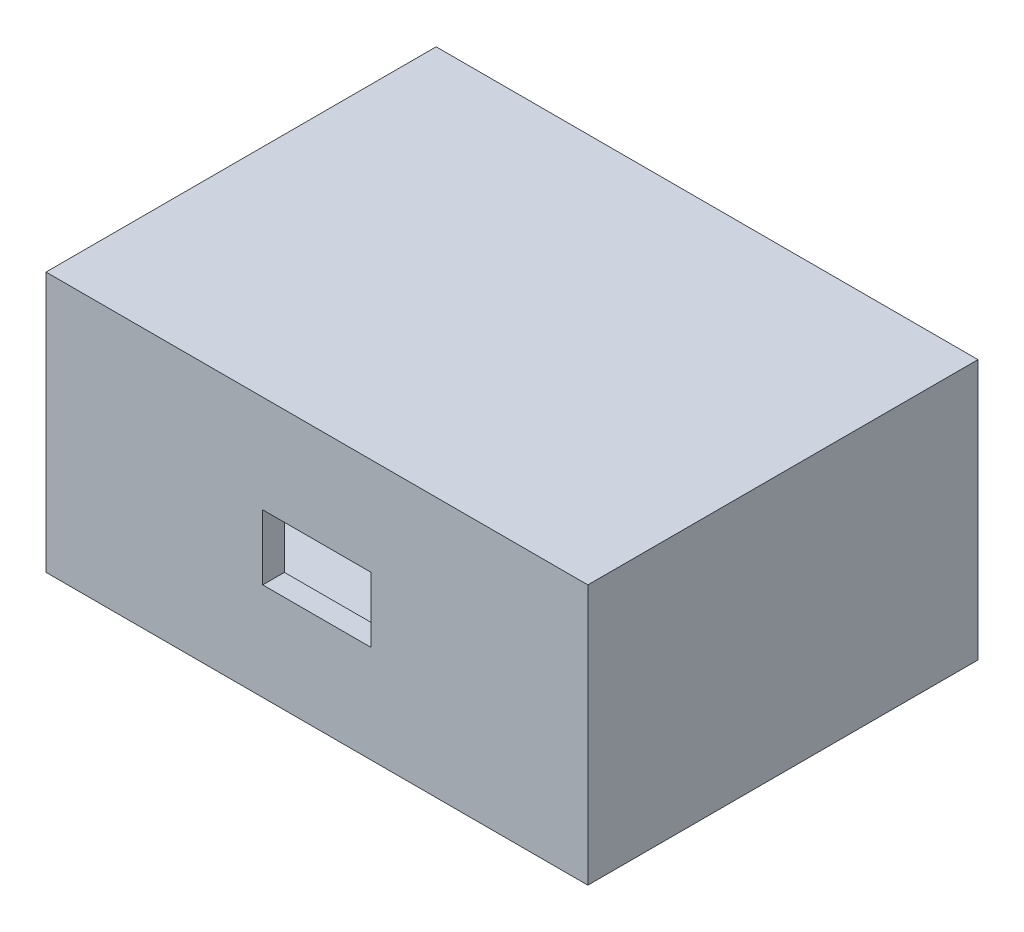
SolidWorks part; units mm, degrees
ref_plane "Front Plane" through (0, 0, 0) normal (0, 0, 1) x (1, 0, 0)
ref_plane "Top Plane" through (0, 0, 0) normal (0, 1, 0) x (1, 0, 0)
ref_plane "Right Plane" through (0, 0, 0) normal (1, 0, 0) x (0, 0, -1)
sketch "Sketch1" plane through (0, 0, 0) normal (0, 0, 1) x (1, 0, 0)
  line L1 (-25, 0) -> (25, 0)
  line L2 (-25, 0) -> (-25, 24)
  line L3 (-25, 24) -> (25, 24)
  line L4 (25, 0) -> (25, 24)
extrude "Boss-Extrude1" add sketch "Sketch1" along normal blind 36
sketch "Sketch2" plane through (0, 0, 0) normal (0, 0, 1) x (1, 0, 0)
  line L1 (-23, 2) -> (23, 2)
  line L2 (-23, 2) -> (-23, 22)
  line L3 (-23, 22) -> (23, 22)
  line L4 (23, 2) -> (23, 22)
extrude "Boss-Extrude2" add sketch "Sketch2" along normal blind 35 from offset 1 separate body offset against normal yes
combine bodies "Combine1" operation type subtract main body 101 bodies to subtract 102
sketch "Sketch3" plane through (0, 0, 0) normal (0, 0, 1) x (1, 0, 0)
  line L1 (-5, 9) -> (5, 9)
  line L2 (-5, 9) -> (-5, 15)
  line L3 (-5, 15) -> (5, 15)
  line L4 (5, 9) -> (5, 15)
extrude "Boss-Extrude3" add sketch "Sketch3" along normal blind 7 from offset 33 separate body
combine bodies "Combine2" operation type subtract main body 103 bodies to subtract 104
